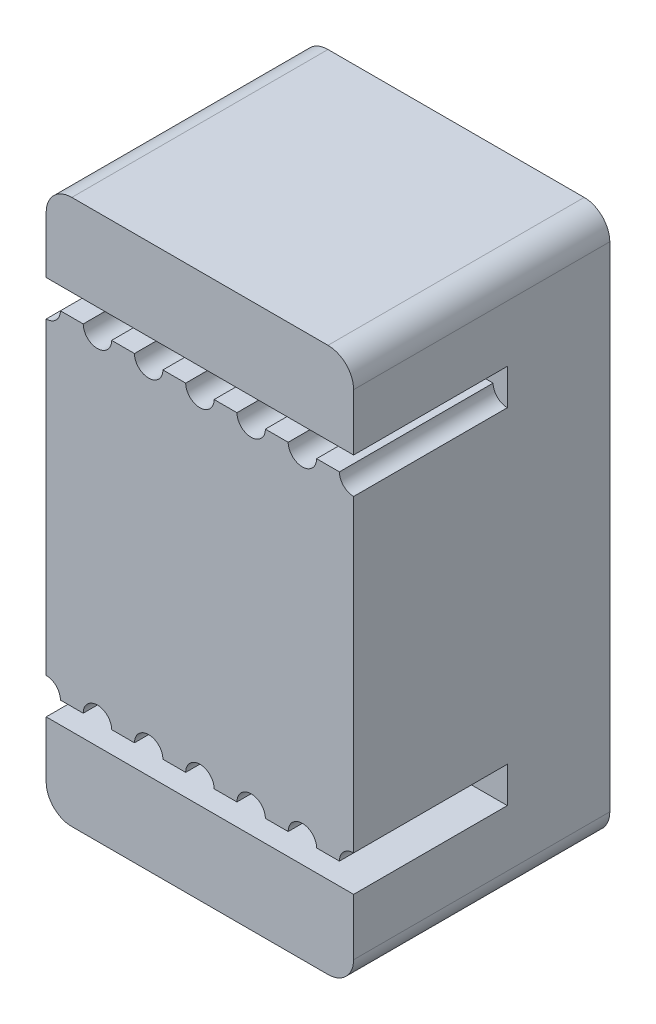
SolidWorks part; units mm, degrees
ref_plane "Front Plane" through (0, 0, 0) normal (0, 0, 1) x (1, 0, 0)
ref_plane "Top Plane" through (0, 0, 0) normal (0, 1, 0) x (1, 0, 0)
ref_plane "Right Plane" through (0, 0, 0) normal (1, 0, 0) x (0, 0, -1)
sketch "Sketch1" plane through (0, 0, 0) normal (0, 0, 1) x (1, 0, 0)
  line L45 (1, 21.27) -> (11, 21.27)
  line L50 (0, 20.27) -> (0, 1)
  line L51 (1, 0) -> (11, 0)
  line L52 (12, 20.27) -> (12, 1)
  arc A42 (11, 21.27) -> (12, 20.27) centre (11, 20.27) cw
  arc A43 (11, 0) -> (12, 1) centre (11, 1) ccw
  arc A44 (0, 1) -> (1, 0) centre (1, 1) ccw
  arc A45 (1, 21.27) -> (0, 20.27) centre (1, 20.27) ccw
extrude "Boss-Extrude1" add sketch "Sketch1" along normal blind 10
sketch "Sketch2" plane through (0, 0, 10) normal (0, 0, 1) x (1, 0, 0)
  line L1 (11.445, 17.215) -> (10.555, 17.215)
  line L2 (9.445, 17.215) -> (8.555, 17.215)
  line L3 (7.445, 17.215) -> (6.555, 17.215)
  line L4 (5.445, 17.215) -> (4.555, 17.215)
  line L5 (0, 18.06) -> (12, 18.06)
  line L6 (12, 18.06) -> (12, 16.66)
  line L7 (0, 18.06) -> (0, 16.66)
  line L8 (3.445, 17.215) -> (2.555, 17.215)
  line L9 (1.445, 17.215) -> (0.555, 17.215)
  line L10 (0, 3.21) -> (12, 3.21)
  line L11 (1.445, 4.055) -> (0.555, 4.055)
  line L12 (3.445, 4.055) -> (2.555, 4.055)
  line L13 (0, 3.21) -> (0, 4.61)
  line L14 (12, 3.21) -> (12, 4.61)
  line L15 (5.445, 4.055) -> (4.555, 4.055)
  line L16 (7.445, 4.055) -> (6.555, 4.055)
  line L17 (9.445, 4.055) -> (8.555, 4.055)
  line L18 (11.445, 4.055) -> (10.555, 4.055)
  arc A0 (9.445, 17.215) -> (10.555, 17.215) centre (10, 17.215) ccw
  arc A1 (11.445, 17.215) -> (12, 16.66) centre (12, 17.215) ccw
  arc A2 (7.445, 17.215) -> (8.555, 17.215) centre (8, 17.215) ccw
  arc A3 (6.555, 17.215) -> (5.445, 17.215) centre (6, 17.215) cw
  arc A4 (4.555, 17.215) -> (3.445, 17.215) centre (4, 17.215) cw
  arc A5 (1.445, 17.215) -> (2.555, 17.215) centre (2, 17.215) ccw
  arc A6 (0.555, 17.215) -> (0, 16.66) centre (0, 17.215) cw
  arc A7 (0.555, 4.055) -> (0, 4.61) centre (0, 4.055) ccw
  arc A8 (1.445, 4.055) -> (2.555, 4.055) centre (2, 4.055) cw
  arc A9 (4.555, 4.055) -> (3.445, 4.055) centre (4, 4.055) ccw
  arc A10 (6.555, 4.055) -> (5.445, 4.055) centre (6, 4.055) ccw
  arc A11 (7.445, 4.055) -> (8.555, 4.055) centre (8, 4.055) cw
  arc A12 (11.445, 4.055) -> (12, 4.61) centre (12, 4.055) cw
  arc A13 (9.445, 4.055) -> (10.555, 4.055) centre (10, 4.055) cw
extrude "Cut-Extrude1" cut sketch "Sketch2" against normal offset from surface (6 mm away) 4 up to face at (6, 10.635, 0)
